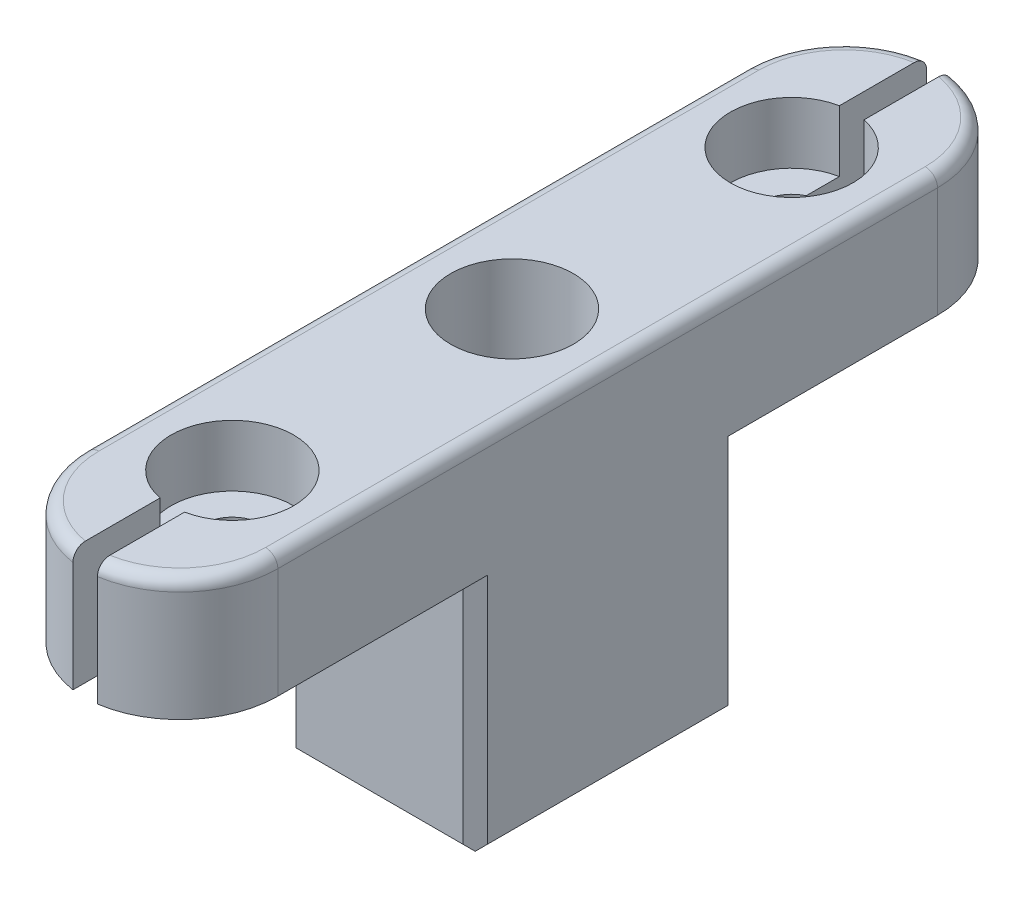
SolidWorks part; units mm, degrees
ref_plane "Plan de face" through (0, 0, 0) normal (0, 0, 1) x (1, 0, 0)
ref_plane "Plan de dessus" through (0, 0, 0) normal (0, 1, 0) x (1, 0, 0)
ref_plane "Plan de droite" through (0, 0, 0) normal (1, 0, 0) x (0, 0, -1)
sketch "Esquisse1" plane through (0, 0, 0) normal (0, 1, 0) x (1, 0, 0)
  line L1 (0, 0) -> (7.8, 0)
  line L2 (0, 0) -> (0, 10.8)
  line L3 (0, 10.8) -> (7.8, 10.8)
  line L4 (7.8, 0) -> (7.8, 10.8)
  dimension "D1" = 10.8
  dimension "D2" = 7.8
extrude "Boss.-Extru.1" add sketch "Esquisse1" along normal blind 15
sketch "Esquisse6" plane through (0, 0, 0) normal (0, -1, 0) x (1, 0, 0)
  line L0 (7.8, -5.4) -> (0, -5.4) construction
  line L1 (7.8, 0) -> (7.8, -10.8) construction
  line L2 (0, -10.8) -> (0, 0) construction
  circle A0 centre (3.9, -5.4) radius 1.05
extrude "Enlèv. mat.-Extru.2" cut sketch "Esquisse6" against normal through all
sketch "Esquisse7" plane through (0, 0, 0) normal (0, -1, 0) x (1, 0, 0)
  line L0 (3.9, -5.4) -> (3.9, -7.68) construction
  line L2 (3.9, -7.68) -> (5.8745, -6.54)
  line L3 (5.8745, -6.54) -> (5.8745, -4.26)
  line L4 (5.8745, -4.26) -> (3.9, -3.12)
  line L5 (3.9, -3.12) -> (1.9255, -4.26)
  line L6 (1.9255, -4.26) -> (1.9255, -6.54)
  line L7 (1.9255, -6.54) -> (3.9, -7.68)
  circle A0 centre (3.9, -5.4) radius 1.9745 construction
extrude "Enlèv. mat.-Extru.3" cut sketch "Esquisse7" against normal blind 2
sketch "Esquisse8" plane through (0, 15, 0) normal (0, 1, 0) x (1, 0, 0)
  circle A0 centre (3.9, 5.4) radius 2.5
extrude "Enlèv. mat.-Extru.4" cut sketch "Esquisse8" against normal blind 11
sketch "Esquisse9" plane through (0, 0, -10.8) normal (0, 0, -1) x (-1, 0, 0)
  line L1 (-7.8, 15) -> (0, 15)
  line L2 (-7.8, 15) -> (-7.8, 10)
  line L3 (-7.8, 10) -> (0, 10)
  line L4 (0, 15) -> (0, 10)
  line L5 (0, 15) -> (0, 0) construction
  dimension "D1" = 5
  dimension "D2" = 7.8
extrude "Boss.-Extru.2" add sketch "Esquisse9" along normal blind 12
sketch "Esquisse10" plane through (0, 0, 0) normal (0, 0, 1) x (1, 0, 0)
  line L1 (0, 15) -> (7.8, 15)
  line L2 (0, 15) -> (0, 10)
  line L3 (0, 10) -> (7.8, 10)
  line L4 (7.8, 15) -> (7.8, 10)
  line L5 (7.8, 15) -> (7.8, 0) construction
  dimension "D1" = 5
  dimension "D2" = 7.8
extrude "Boss.-Extru.3" add sketch "Esquisse10" along normal blind 12
sketch "Esquisse11" plane through (0, 10, 0) normal (0, -1, 0) x (1, 0, 0)
  line L0 (3.9, -10.8) -> (3.9, -16.8) construction
  line L1 (7.8, -10.8) -> (0, -10.8) construction
  line L2 (3.9, 0) -> (3.9, 12) construction
  line L4 (0, 0) -> (7.8, 0) construction
  line L6 (0, 12) -> (7.8, 12) construction
  line L7 (3.9, 0) -> (3.9, 6) construction
  circle A1 centre (3.9, -16.8) radius 1.2
  circle A2 centre (3.9, 6) radius 1.2
extrude "Enlèv. mat.-Extru.5" cut sketch "Esquisse11" against normal through all
sketch "Esquisse15" plane through (0, 15, 0) normal (0, 1, 0) x (1, 0, 0)
  line L0 (3.9, -12) -> (3.9, -7.2) construction
  line L1 (7.8, -12) -> (0, -12) construction
  line L2 (3.9, -12) -> (4.4, -12) construction
  line L3 (3.9, -12) -> (3.4, -12) construction
  line L5 (4.4, -12) -> (3.4, -12)
  line L6 (4.4, -12) -> (4.4, -7.0909)
  line L7 (4.4, -7.0909) -> (3.4, -7.0909)
  line L8 (3.4, -12) -> (3.4, -7.0909)
  circle A0 centre (3.9, -6) radius 1.2 construction
  dimension "D1" = 4.9091
  dimension "D2" = 1
extrude "Enlèv. mat.-Extru.6" cut sketch "Esquisse15" against normal through all
sketch "Esquisse16" plane through (0, 15, 0) normal (0, 1, 0) x (1, 0, 0)
  circle A0 centre (3.9, 16.8) radius 2.5
  circle A1 centre (3.9, -6) radius 2.5
extrude "Enlèv. mat.-Extru.7" cut sketch "Esquisse16" against normal blind 2.5
sketch "Esquisse17" plane through (0, 15, 0) normal (0, 1, 0) x (1, 0, 0)
  line L0 (3.9, 22.8) -> (4.4, 22.8) construction
  line L1 (4.4, 22.8) -> (3.4, 22.8)
  line L2 (0, 22.8) -> (7.8, 22.8) construction
  line L3 (3.9, 22.8) -> (3.4, 22.8) construction
  line L4 (3.4, 22.8) -> (3.4, 17.89)
  line L5 (3.4, 17.89) -> (4.4, 17.89)
  line L6 (4.4, 17.89) -> (4.4, 22.8)
extrude "Enlèv. mat.-Extru.8" cut sketch "Esquisse17" against normal blind 10
fillet "Congé3" radius 4 4 edges at (7.8, 12.5, 12) (7.8, 12.5, -22.8) (0, 12.5, 12) (0, 12.5, -22.8)
chamfer "Chanfrein1" distance 0.5 angle 45 4 edges at (3.9, 0, -10.8) (0, 0, -5.4) (7.8, 0, -5.4) (3.9, 0, 0)
chamfer "Chanfrein2" distance 0.5 angle 45 4 edges at (0, 5.25, 0) (7.8, 5.25, 0) (7.8, 5.25, -10.8) (0, 5.25, -10.8)
fillet "Congé5" radius 0.5 6 edges at (0.9668, 15, -21.4529) (6.8332, 15, -21.4529) (7.8, 15, -5.4) (6.8332, 15, 10.6529) (0.9668, 15, 10.6529) (0, 15, -5.4)
